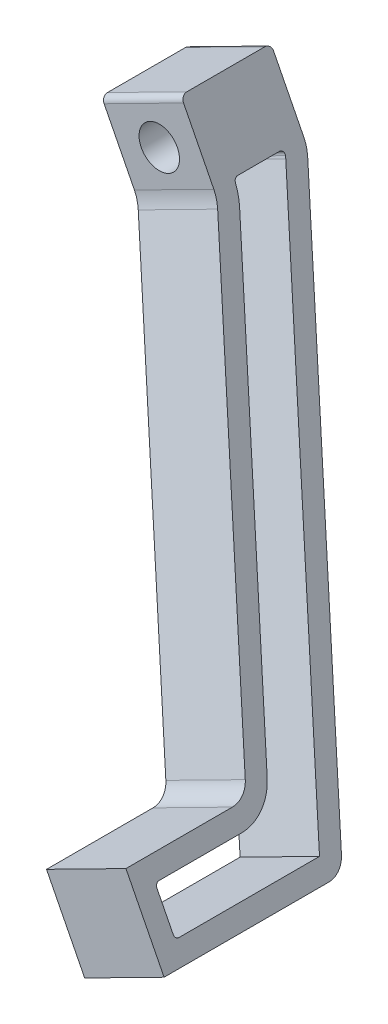
SolidWorks part; units mm, degrees
ref_plane "Front Plane" through (0, 0, 0) normal (0, 0, 1) x (1, 0, 0)
ref_plane "Top Plane" through (0, 0, 0) normal (0, 1, 0) x (1, 0, 0)
ref_plane "Right Plane" through (0, 0, 0) normal (1, 0, 0) x (0, 0, -1)
ref_plane "Plane1" through (627.0375, 0, 0) normal (-1, 0, 0) x (0, 0, 1)
ref_plane "Plane2" through (0, 845.4923, 0) normal (0, 1, 0) x (1, 0, 0)
ref_axis "Axis1" through (627.0375, 845.4923, 1293.2699) along (0, 0, 1)
ref_plane "Plane3" through (839.8175, 426.9856, 0) normal (-0.8914, -0.4532, 0) x (0, 0, 1)
sketch "Sketch2" plane through (0, 0, 1293.5874) normal (0, 0, -1) x (-1, 0, 0)
  line L0 (-627.0375, 863.4923) -> (-627.0375, 827.4923) construction
  line L1 (-646.0375, 863.4923) -> (-608.0375, 863.4923) construction
  line L2 (-608.0375, 827.4923) -> (-646.0375, 827.4923) construction
  point P6 (-627.0375, 845.4923)
sketch "Sketch3" plane through (0, 0, 1293.5874) normal (0, 0, -1) x (-1, 0, 0)
  line L0 (-617.4102, 863.4923) -> (-636.6648, 827.4923) construction
  line L1 (-608.0375, 827.4923) -> (-646.0375, 827.4923) construction
  line L2 (-633.8616, 832.7333) -> (-624.0627, 827.4923) construction
  line L3 (-620.2133, 858.2513) -> (-630.0123, 863.4923) construction
  line L4 (-646.0375, 863.4923) -> (-608.0375, 863.4923) construction
  line L5 (-627.0375, 863.4923) -> (-627.0375, 827.4923) construction
  line L6 (-630.0123, 863.4923) -> (-643.6606, 837.9742) construction
  line L7 (-643.6606, 837.9742) -> (-633.8616, 832.7333) construction
  line L8 (-620.2133, 858.2513) -> (-610.4144, 853.0104) construction
  line L9 (-610.4144, 853.0104) -> (-624.0627, 827.4923) construction
  line L10 (-641.884, 841.296) -> (-622.286, 830.8141) construction
  line L11 (-637.2028, 838.7923) -> (-640.0375, 833.4923) construction
  line L12 (-631.789, 860.1706) -> (-612.191, 849.6886) construction
  line L13 (-614.0375, 857.4923) -> (-616.8722, 852.1923) construction
  line L14 (-634.7375, 854.6576) -> (-640.0375, 857.4923) construction
  point P6 (-627.0375, 845.4923)
  point P22 (-632.085, 836.055)
  point P28 (-621.99, 854.9296)
  dimension "D1" = 22.225
  dimension "D2" = 28.14
sketch "Sketch4" plane through (839.8547, 426.9124, 0) normal (0.8914, 0.4532, 0) x (0, 0, -1)
  line L0 (-1203.4253, 589.2353) -> (-1225.8915, 589.2353) construction
  line L1 (-1293.5874, 459.0746) -> (-1293.5874, 480.0746)
  line L2 (-1214.6584, 589.2353) -> (-1214.6584, 579.2353) construction
  line L3 (-1256.3458, 469.5746) -> (-1293.5874, 469.5746) construction
  line L4 (-1203.4253, 599.2353) -> (-1203.4253, 579.2353)
  line L5 (-1214.6584, 579.2353) -> (-1256.3458, 469.5746) construction
  line L6 (-1203.4253, 599.2353) -> (-1225.8915, 599.2353)
  line L7 (-1225.8915, 599.2353) -> (-1225.8915, 579.2353)
  line L8 (-1225.8915, 579.2353) -> (-1263.5874, 480.0746)
  line L9 (-1203.4253, 579.2353) -> (-1225.8915, 579.2353) construction
  line L10 (-1203.4253, 579.2353) -> (-1249.1043, 459.0746)
  line L14 (-1293.5874, 480.0746) -> (-1263.5874, 480.0746)
  line L15 (-1293.5874, 459.0746) -> (-1249.1043, 459.0746)
  point P5 (-1214.6584, 589.2353)
  point P10 (-1293.5874, 469.5746)
  point P14 (-1203.4253, 589.2353)
  point P19 (-1221.4246, 459.0746)
  point P20 (-1214.6584, 579.2353)
  point P21 (-1233.4609, 480.0746)
  point P23 (-1232.7815, 480.0746)
  dimension "D1" = 21
  dimension "D2" = 20
  dimension "D3" = 90.1621
  dimension "D4" = 30
  dimension "D5" = 21
  dimension "D6" = 119.6607
extrude "Boss-Extrude1" add sketch "Sketch4" along normal mid plane 22.225
sketch "Sketch5" plane through (0, 0, 1203.4253) normal (0, 0, -1) x (-1, 0, 0)
  line L0 (-578.1793, 966.1085) -> (-567.4322, 938.2078) construction
  point P4 (-572.8057, 952.1581)
sketch "Sketch8" plane through (0, 0, 1203.4253) normal (0, 0, -1) x (-1, 0, 0)
  point P0 (-572.8057, 952.1581)
hole_wizard "3/8 Clearance Hole1" positions "Sketch8" profile "Sketch7" hole size "3/8" standard "ANSI Inch" end condition through all
sketch "Sketch7" plane through (572.8057, 952.1581, 1203.4253) normal (1, 0, 0) x (0, 1, 0)
  line L0 (0, 0) -> (0, 90.1621)
  line L1 (0, 90.1621) -> (5.0419, 90.1621)
  line L2 (5.0419, 90.1621) -> (5.0419, 0)
  line L5 (5.0419, 0) -> (0, 0)
  line L11 (0, -6.35) -> (0, 107.95) construction
  dimension "Thru Hole Dia." = 10.0838
  dimension "Thru Hole Depth" = 90.1621
fillet "Fillet1" radius 10 2 edges at (577.3379, 943.2441, 1225.8915) (577.3379, 943.2441, 1203.4253)
fillet "Fillet2" radius 5 2 edges at (631.7962, 836.1326, 1249.1043) (622.2788, 854.852, 1263.5874)
fillet "Fillet3" radius 1.5 2 edges at (568.2736, 961.0721, 1203.4253) (568.2736, 961.0721, 1225.8915)
sketch "Sketch9" plane through (849.7232, 432.022, 0) normal (0.8914, 0.4532, 0) x (0, 0, -1)
  line L0 (-1220.8915, 580.9897) -> (-1208.4253, 580.9897)
  line L9 (-1267.0357, 474.9924) -> (-1288.5874, 474.9924)
  line L10 (-1267.0357, 474.9924) -> (-1288.5874, 474.9924)
  line L11 (-1288.5874, 463.9924) -> (-1252.5527, 463.9924)
  line L12 (-1288.5874, 463.9924) -> (-1252.5527, 463.9924)
  line L16 (-1208.4253, 580.9897) -> (-1208.4253, 594.1531)
  line L17 (-1208.4253, 594.1531) -> (-1220.8915, 594.1531)
  line L18 (-1220.8915, 594.1531) -> (-1220.8915, 580.9897)
  line L19 (-1221.8705, 575.6597) -> (-1257.6884, 481.439)
  line L21 (-1288.5874, 474.9924) -> (-1288.5874, 463.9924)
  line L23 (-1252.5527, 463.9924) -> (-1208.7516, 579.213)
  line L27 (-1221.8705, 575.6597) -> (-1257.6884, 481.439)
  line L29 (-1288.5874, 474.9924) -> (-1288.5874, 463.9924)
  line L31 (-1252.5527, 463.9924) -> (-1208.7516, 579.213)
  arc A6 (-1267.0357, 474.9924) -> (-1257.6884, 481.439) centre (-1267.0357, 484.9924) ccw
  arc A7 (-1267.0357, 474.9924) -> (-1257.6884, 481.439) centre (-1267.0357, 484.9924) ccw
  arc A12 (-1221.8705, 575.6597) -> (-1220.8915, 580.9897) centre (-1235.8915, 580.9897) ccw
  arc A15 (-1208.7516, 579.213) -> (-1208.4253, 580.9897) centre (-1213.4253, 580.9897) ccw
  arc A16 (-1221.8705, 575.6597) -> (-1220.8915, 580.9897) centre (-1235.8915, 580.9897) ccw
  arc A19 (-1208.7516, 579.213) -> (-1208.4253, 580.9897) centre (-1213.4253, 580.9897) ccw
  dimension "D1" = 5
extrude "Cut-Extrude1" cut sketch "Sketch9" against normal up to next
fillet "Fillet4" radius 1 4 edges at (576.5055, 944.8813, 1208.4253) (576.5055, 944.8813, 1220.8915) (629.5302, 840.5896, 1288.5874) (624.5448, 850.395, 1288.5874)
equation "\"Steering_Arm_Thickness\"= 1in"
